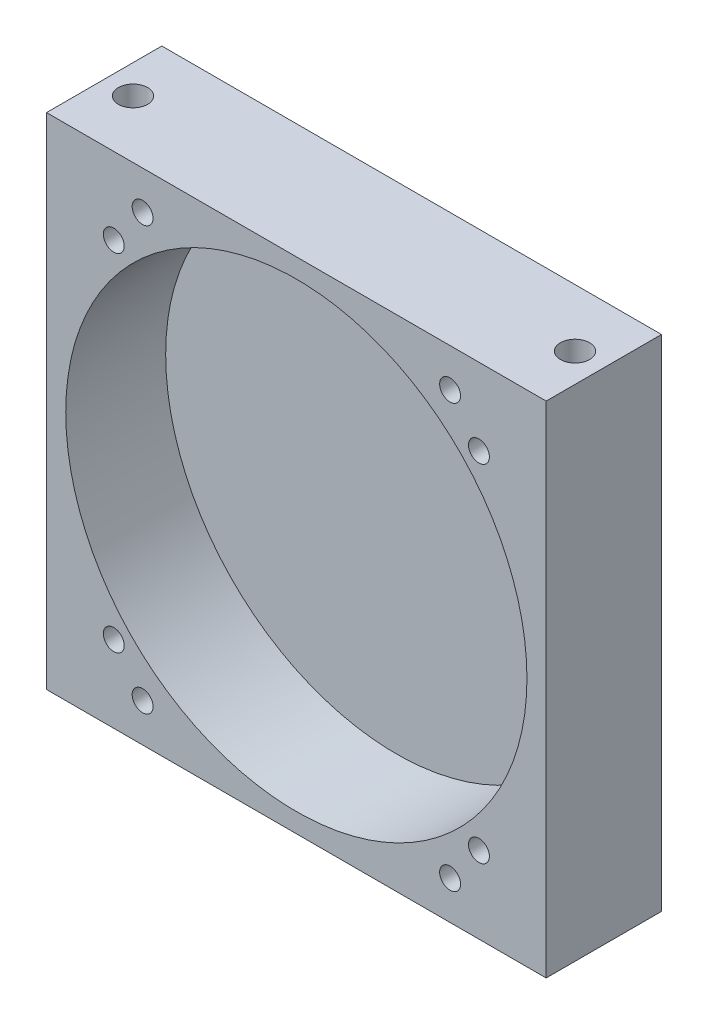
SolidWorks part; units mm, degrees
material "6061-T6 (SS)"
ref_plane "Front Plane" through (0, 0, 0) normal (0, 0, 1) x (1, 0, 0)
ref_plane "Top Plane" through (0, 0, 0) normal (0, 1, 0) x (1, 0, 0)
ref_plane "Right Plane" through (0, 0, 0) normal (1, 0, 0) x (0, 0, -1)
sketch "Sketch1" plane through (0, 0, 0) normal (0, 0, 1) x (1, 0, 0)
  line L1 (41.275, -41.275) -> (-41.275, -41.275)
  line L2 (41.275, -41.275) -> (41.275, 41.275)
  line L3 (41.275, 41.275) -> (-41.275, 41.275)
  line L4 (-41.275, -41.275) -> (-41.275, 41.275)
  line L5 (41.275, -41.275) -> (-41.275, 41.275) construction
  line L6 (41.275, 41.275) -> (-41.275, -41.275) construction
  point P0 (0, 0)
  dimension "D1" = 82.55
  dimension "D2" = 82.55
extrude "Boss-Extrude1" add sketch "Sketch1" along normal blind 19.05
sketch "Sketch2" plane through (0, 0, 19.05) normal (0, 0, 1) x (1, 0, 0)
  circle A0 centre (0, 0) radius 38.1
  dimension "D1" = 76.2
extrude "Cut-Extrude1" cut sketch "Sketch2" against normal blind 16.51
hole_wizard "#10-32 Tapped Hole1" positions "Sketch4" profile "Sketch3" tap size "#10-32" standard "ANSI Inch"
sketch "Sketch4" plane through (0, 41.275, 0) normal (0, 1, 0) x (-1, 0, 0)
  line L0 (-36.5125, 9.525) -> (0, 0) construction
  line L1 (0, 0) -> (36.5125, 9.525) construction
  line L3 (-41.275, 0) -> (41.275, 0) construction
  point P0 (36.5125, 9.525)
  point P1 (-36.5125, 9.525)
  dimension "D1" = 73.025
  dimension "D2" = 9.525
sketch "Sketch3" plane through (-36.5125, 41.275, 9.525) normal (1, 0, 0) x (0, 0, 1)
  line L0 (0, 0) -> (0, 20.2633)
  line L1 (0, 20.2633) -> (2.0193, 19.05)
  line L2 (2.0193, 19.05) -> (2.0193, 18.288)
  line L3 (2.0193, 18.288) -> (2.413, 18.288)
  line L4 (2.413, 18.288) -> (2.413, 0)
  line L5 (2.413, 0) -> (0, 0)
  line L10 (0, 20.2633) -> (-2.0193, 19.05) construction
  line L11 (0, -6.35) -> (0, 107.95) construction
  dimension "Tap Drill Dia." = 4.0386
  dimension "Tap Drill Depth" = 19.05
  dimension "Thread Major Dia." = 4.826
  dimension "Thread Depth" = 18.288
  dimension "Drill Angle" = 118
mirror "Mirror1" about plane through (0, 0, 0) normal (0, 1, 0) of "#10-32 Tapped Hole1"
hole_wizard "#8-32 Tapped Hole1" positions "Sketch6" profile "Sketch5" tap size "#8-32" standard "ANSI Inch"
sketch "Sketch6" plane through (0, 0, 19.05) normal (0, 0, 1) x (1, 0, 0)
  line L0 (25.4, -34.925) -> (-25.4, 34.925) construction
  line L3 (25.4, 34.925) -> (-25.4, -34.925) construction
  point P0 (25.4, -34.925)
  point P1 (-25.4, -34.925)
  point P3 (-25.4, 34.925)
  point P5 (25.4, 34.925)
  dimension "D1" = 50.8
  dimension "D2" = 69.85
sketch "Sketch5" plane through (25.4, -34.925, 19.05) normal (1, 0, 0) x (0, -1, 0)
  line L0 (0, 0) -> (0, 17.0398)
  line L1 (0, 17.0398) -> (1.7272, 16.002)
  line L2 (1.7272, 16.002) -> (1.7272, 0)
  line L5 (1.7272, 0) -> (0, 0)
  line L10 (0, 17.0398) -> (-1.7272, 16.002) construction
  line L11 (0, -6.35) -> (0, 107.95) construction
  dimension "Tap Drill Dia." = 3.4544
  dimension "Tap Drill Depth" = 16.002
  dimension "Drill Angle" = 118
cosmetic thread "Hole Thread1" parameters "D1"=8.382, "D2"=4.1656
cosmetic thread "Hole Thread2" parameters "D1"=8.382, "D2"=4.1656
cosmetic thread "Hole Thread3" parameters "D1"=8.382, "D2"=4.1656
cosmetic thread "Hole Thread4" parameters "D1"=8.382, "D2"=4.1656
hole_wizard "#8-32 Tapped Hole2" positions "Sketch8" profile "Sketch7" tap size "#8-32" standard "ANSI Inch"
sketch "Sketch8" plane through (0, 0, 19.05) normal (0, 0, 1) x (1, 0, 0)
  line L1 (-30.1625, 28.575) -> (30.1625, 28.575)
  line L2 (-30.1625, 28.575) -> (-30.1625, -28.575)
  line L3 (-30.1625, -28.575) -> (30.1625, -28.575)
  line L4 (30.1625, 28.575) -> (30.1625, -28.575)
  line L5 (-30.1625, 28.575) -> (30.1625, -28.575) construction
  line L6 (-30.1625, -28.575) -> (30.1625, 28.575) construction
  point P2 (30.1625, -28.575)
  point P79 (-30.1625, 28.575)
  point P80 (-30.1625, -28.575)
  point P81 (30.1625, 28.575)
  dimension "D1" = 60.325
  dimension "D2" = 57.15
sketch "Sketch7" plane through (30.1625, -28.575, 19.05) normal (1, 0, 0) x (0, -1, 0)
  line L0 (0, 0) -> (0, 17.0398)
  line L1 (0, 17.0398) -> (1.7272, 16.002)
  line L2 (1.7272, 16.002) -> (1.7272, 0)
  line L5 (1.7272, 0) -> (0, 0)
  line L10 (0, 17.0398) -> (-1.7272, 16.002) construction
  line L11 (0, -6.35) -> (0, 107.95) construction
  dimension "Tap Drill Dia." = 3.4544
  dimension "Tap Drill Depth" = 16.002
  dimension "Drill Angle" = 118
cosmetic thread "Hole Thread5" parameters "D1"=8.382, "D2"=4.1656
cosmetic thread "Hole Thread6" parameters "D1"=8.382, "D2"=4.1656
cosmetic thread "Hole Thread7" parameters "D1"=8.382, "D2"=4.1656
cosmetic thread "Hole Thread8" parameters "D1"=8.382, "D2"=4.1656
